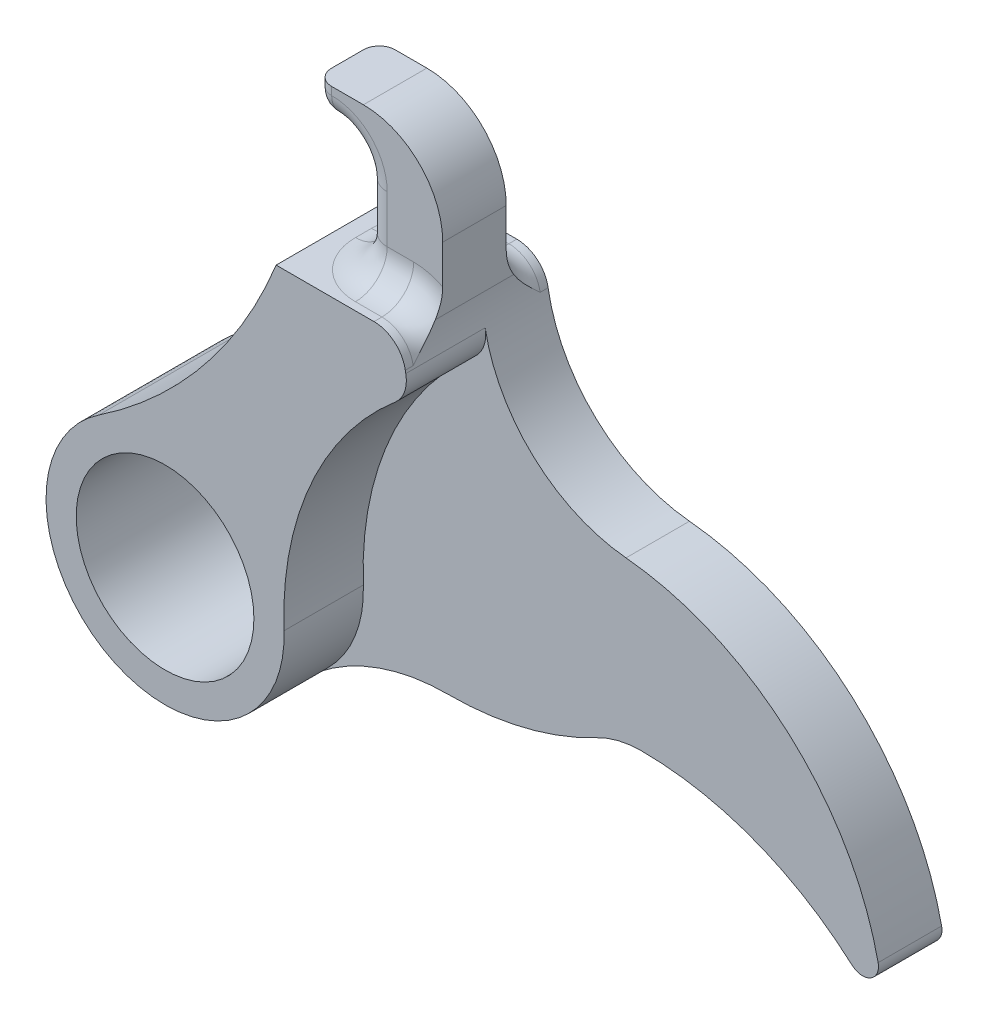
SolidWorks part; units mm, degrees
ref_plane "Спереди" through (0, 0, 0) normal (0, 0, 1) x (1, 0, 0)
ref_plane "Сверху" through (0, 0, 0) normal (0, 1, 0) x (1, 0, 0)
ref_plane "Справа" through (0, 0, 0) normal (1, 0, 0) x (0, 0, -1)
sketch "base" plane through (0, 0, 0) normal (0, 0, 1) x (1, 0, 0)
  line L0 (0, -25) -> (-25, -20) construction
  line L1 (0, 0) -> (9.5671, -23.097) construction
  line L2 (0, 0) -> (-9.5671, -23.097) construction
  line L3 (0, 0) -> (0, -25) construction
  line L4 (0, 0) -> (-2.4504, -24.8796) construction
  line L6 (0, 0) -> (-4.8773, -24.5196) construction
  line L7 (0, -25) -> (25, -20) construction
  line L11 (0, 0) -> (-7.2571, -23.9235) construction
  line L14 (0, 0) -> (7.2571, -23.9235) construction
  line L16 (0, 0) -> (4.8773, -24.5196) construction
  line L18 (0, 0) -> (2.4504, -24.8796) construction
  line L19 (-9.5671, -23.097) -> (9.5671, -23.097) construction
  arc A0 (-7.6537, -18.4776) -> (7.6537, -18.4776) centre (0, 0) ccw construction
  circle A1 centre (0, -25) radius 5 construction
  arc A6 (-9.5671, -23.097) -> (9.5671, -23.097) centre (0, 0) ccw construction
  point P12 (0, -20)
  dimension "D5" = 45
  dimension "D12" = 20
  dimension "ArmA" = 25
  dimension "ArmB" = 25.4951
  dimension "R" = 5
  dimension "base_offset" = 25
  dimension "stick_leverage" = 25
sketch "base-curve" plane through (0, 0, 0) normal (0, 0, 1) x (1, 0, 0)
  line L0 (0, -20) -> (0, -25) construction
  line L1 (0, 0) -> (-2.4504, -24.8796) construction
  line L2 (0, 0) -> (2.4504, -24.8796) construction
  line L5 (-25, -20) -> (0, -20) construction
  line L6 (0, -20) -> (25, -20) construction
  line L7 (10, -20) -> (10, 0) construction
  line L8 (-10, -20) -> (-10, 0) construction
  line L9 (-10, 0) -> (10, 0) construction
  line L10 (-25, -20) -> (-10, 0) construction
  line L11 (10, 0) -> (25, -20) construction
  line L13 (0, 0) -> (-4.8773, -24.5196) construction
  line L14 (0, 0) -> (4.8773, -24.5196) construction
  line L15 (0, 0) -> (-7.2571, -23.9235) construction
  line L16 (0, 0) -> (-9.5671, -23.097) construction
  line L17 (-2.2605, -20.5401) -> (-4.3096, -21.5787)
  line L18 (-4.3096, -21.5787) -> (-6.5058, -22.3844)
  line L19 (-6.5058, -22.3844) -> (-9.5586, -23.0612)
  line L20 (-9.5586, -23.0612) -> (-12.1501, -23.2901)
  line L21 (-2.5877, -26.2729) -> (-4.3096, -21.5787) construction
  line L22 (-8.4763, -27.9427) -> (-9.5586, -23.0612) construction
  line L23 (-5.4235, -27.2658) -> (-6.5058, -22.3844) construction
  line L24 (-11.7101, -28.2707) -> (-12.1501, -23.2901) construction
  line L25 (-22.6762, -27.1309) -> (-1.5492, -20.2461) construction
  line L26 (0, 0) -> (7.2571, -23.9235) construction
  line L27 (0, 0) -> (9.5671, -23.097) construction
  circle A0 centre (0, -25) radius 5 construction
  circle A1 centre (2.6465, -26.87) radius 5 construction
  circle A2 centre (-2.5877, -26.2729) radius 5 construction
  circle A4 centre (-5.4235, -27.2658) radius 5 construction
  circle A5 centre (-8.4763, -27.9427) radius 5 construction
  circle A6 centre (-25, -20) radius 7.5 construction
  circle A7 centre (-11.7101, -28.2707) radius 5 construction
  circle A8 centre (5.6576, -28.4428) radius 5 construction
  circle A9 centre (8.9988, -29.6652) radius 5 construction
  circle A10 centre (12.6286, -30.488) radius 5 construction
  point P3 (2.4504, -24.8796)
  point P11 (2.6465, -26.87)
  point P24 (-2.4504, -24.8796)
  point P25 (4.8773, -24.5196)
  point P27 (-4.8773, -24.5196)
  point P33 (-7.2571, -23.9235)
  point P36 (-9.5671, -23.097)
  point P39 (-2.5877, -26.2729)
  point P40 (5.6576, -28.4428)
  point P41 (-5.4235, -27.2658)
  point P42 (-8.4763, -27.9427)
  point P43 (-11.7101, -28.2707)
  point P64 (7.2571, -23.9235)
  point P65 (8.9988, -29.6652)
  point P68 (9.5671, -23.097)
  point P69 (12.6286, -30.488)
  dimension "D13" = 15
  dimension "spring" = 20
  dimension "b_long" = 53.13
  dimension "b_short" = 53.13
  dimension "D3" = 1.4
  dimension "D4" = 2.8
  dimension "D5" = 4.2
  dimension "D6" = 5.6
  dimension "D2" = 2
  dimension "D7" = 4
  dimension "D8" = 6
  dimension "D9" = 8
sketch "Эскиз2" plane through (0, 0, 0) normal (0, 0, 1) x (1, 0, 0)
  line L0 (-11.7101, -28.2707) -> (-12.1749, -23.0095) construction
  line L1 (-10, 0) -> (-18, 0) construction
  line L3 (-2.2605, -20.5401) -> (-4.3096, -21.5787) construction
  line L4 (0, -25) -> (0, 0) construction
  line L10 (-4.3096, -21.5787) -> (-6.5058, -22.3844) construction
  line L11 (-22.6602, -27.1257) -> (-1.8719, -20.2995) construction
  line L12 (-6.5058, -22.3844) -> (-9.5586, -23.0612) construction
  line L13 (-9.5586, -23.0612) -> (-12.1501, -23.2901) construction
  line L14 (-2.2605, -20.5401) -> (-4.3096, -21.5787) construction
  line L15 (-4.3096, -21.5787) -> (-6.5058, -22.3844) construction
  line L16 (-6.5058, -22.3844) -> (-9.5586, -23.0612) construction
  line L17 (-9.5586, -23.0612) -> (-12.1501, -23.2901) construction
  line L19 (0, -25) -> (0, -40) construction
  line L20 (0, -40) -> (15.3209, -27.1442) construction
  line L21 (-18, 0) -> (-15, 0)
  line L23 (-10, 0) -> (-10, 7)
  line L24 (-10, 7) -> (-15, 7)
  line L25 (-15, 0) -> (-15, 7)
  circle A0 centre (-25, -20) radius 7.5 construction
  arc A1 (-2.8021, -20.6945) -> (-12.1749, -23.0095) centre (-12.1425, -3.0096) cw
  arc A2 (-29.1682, -13.7649) -> (-20.3156, -25.8571) centre (-25, -20) ccw
  arc A3 (15.3209, -27.1442) -> (0, -20) centre (0, -40) ccw
  arc A5 (-29.1682, -13.7649) -> (-18, 0) centre (-45.8408, 11.1755) ccw
  arc A6 (-7.6537, -18.4776) -> (7.6537, -18.4776) centre (0, 0) ccw construction
  arc A7 (-9.5671, -23.097) -> (9.5671, -23.097) centre (0, 0) ccw construction
  arc A8 (-2.8021, -20.6945) -> (0, -20) centre (0, -26) cw
  arc A10 (15.3209, -27.1442) -> (-0.9516, -9.9546) centre (-2.6644, -27.8729) ccw
  arc A11 (-0.9516, -9.9546) -> (-10, 0) centre (0, 0) cw
  arc A13 (-16.899, -23.8901) -> (-9.55, -2.9661) centre (2.4797, -18.9437) cw construction
  arc A17 (-20.3156, -25.8571) -> (-12.1749, -23.0095) centre (-12.1959, -36.0095) cw
  point P48 (-2.5877, -26.2729)
  point P52 (-5.4235, -27.2658)
  point P54 (-8.4763, -27.9427)
  point P56 (-11.7101, -28.2707)
  dimension "D2" = 6
  dimension "D3" = 5
  dimension "D4" = 3
  dimension "D5" = 30
  dimension "D6" = 50
  dimension "D8" = 18
  dimension "80" = 20
  dimension "D9" = 20
  dimension "D10" = 20
  dimension "D11" = 7
  dimension "D14" = 13
  dimension "D7" = 10
  dimension "D1" = 8
extrude "Бобышка-Вытянуть1" add sketch "Эскиз2" along normal blind 9
sketch "Эскиз6" plane through (0, 0, 9) normal (0, 0, 1) x (1, 0, 0)
  arc A0 (-9.55, -2.9661) -> (-16.899, -23.8901) centre (2.4797, -18.9437) ccw construction
  arc A1 (-9.55, -2.9661) -> (-16.899, -23.8901) centre (2.4797, -18.9437) ccw
  arc A2 (15.3209, -27.1442) -> (-0.9516, -9.9546) centre (-2.6644, -27.8729) ccw construction
  arc A3 (-12.1749, -23.0095) -> (-20.3156, -25.8571) centre (-12.1959, -36.0095) ccw construction
  arc A4 (15.3209, -27.1442) -> (0, -20) centre (0, -40) ccw construction
  arc A5 (-10, 0) -> (-0.9516, -9.9546) centre (0, 0) ccw construction
  arc A6 (15.3209, -27.1442) -> (-0.9516, -9.9546) centre (-2.6644, -27.8729) ccw
  arc A7 (-9.55, -2.9661) -> (-0.9516, -9.9546) centre (0, 0) ccw
  arc A8 (15.3209, -27.1442) -> (0, -20) centre (0, -40) ccw
  arc A9 (-12.1749, -23.0095) -> (-2.8021, -20.6945) centre (-12.1425, -3.0096) ccw construction
  arc A10 (0, -20) -> (-2.8021, -20.6945) centre (0, -26) ccw construction
  arc A11 (-12.1749, -23.0095) -> (-16.899, -23.8901) centre (-12.1959, -36.0095) ccw
  arc A12 (-12.1749, -23.0095) -> (-2.8021, -20.6945) centre (-12.1425, -3.0096) ccw
  arc A13 (0, -20) -> (-2.8021, -20.6945) centre (0, -26) ccw
extrude "Вырез-Вытянуть1" cut sketch "Эскиз6" against normal blind 5
sketch "Эскиз12" plane through (-15, 0, 0) normal (-1, 0, 0) x (0, 0, 1)
  line L0 (9, 0) -> (0, 0) construction
  line L1 (0, 7) -> (2.5, 7)
  line L2 (0, 7) -> (0, 0)
  line L3 (0, 0) -> (2.5, 0)
  line L4 (2.5, 7) -> (2.5, 0)
  line L5 (4.5, 0) -> (4.5, 7) construction
  line L6 (9, 7) -> (0, 7) construction
  line L7 (6.5, 7) -> (6.5, 0)
  line L8 (9, 0) -> (6.5, 0)
  line L9 (9, 7) -> (9, 0)
  line L10 (9, 7) -> (6.5, 7)
  dimension "D1" = 4
extrude "Вырез-Вытянуть3" cut sketch "Эскиз12" against normal through all
fillet "Скругление11" radius 2 2 edges at (-10, 0, 1.25) (-10, 0, 7.75)
fillet "Скругление1" radius 1 1 edges at (15.3209, -27.1442, 2)
sketch "Эскиз10" plane through (0, 7, 0) normal (0, 1, 0) x (-1, 0, 0)
  line L0 (10, 6.5) -> (15, 6.5) construction
  line L1 (10, 2.5) -> (18, 2.5)
  line L2 (10, 2.5) -> (10, 6.5)
  line L3 (10, 6.5) -> (18, 6.5)
  line L4 (18, 2.5) -> (18, 6.5)
  line L5 (10, 6.5) -> (10, 2.5) construction
  line L6 (15, 6.5) -> (15, 2.5) construction
  dimension "D1" = 3
extrude "Бобышка-Вытянуть3" add sketch "Эскиз10" along normal blind 2
fillet "Скругление5" radius 5 1 edges at (-10, 9, 4.5)
fillet "Скругление10" radius 7.5 1 edges at (-16.899, -23.8901, 6.5)
fillet "Скругление14" radius 2 1 edges
fillet "Скругление15" radius 1.5 6 edges at (-15.5858, 6.4142, 2.5) (-15.5858, 6.4142, 6.5)
fillet "Скругление16" radius 2 7 edges at (-10.5412, -0.4725, 6.5) (-12.6661, 0, 6.5) (-10.5412, -0.4725, 2.5) (-12.6661, 0, 2.5) (-14.5607, 0, 2.9393) (-15, 0, 4.5) (-14.5607, 0, 6.0607)
fillet "Скругление17" radius 1 5 edges at (-18, 8.75, 2.5) (-18, 7.4393, 2.9393) (-18, 7, 4.5) (-18, 8.75, 6.5) (-18, 7.4393, 6.0607)
fillet "Скругление18" radius 2 1 edges at (-9.55, -2.9661, 6.5)
sketch "Эскиз11" plane through (0, 0, 9) normal (0, 0, 1) x (1, 0, 0)
  circle A0 centre (-25, -20) radius 5.5 construction
  arc A1 (-29.1682, -13.7649) -> (-20.3156, -25.8571) centre (-25, -20) ccw construction
  circle A2 centre (-25, -20) radius 5.6
  dimension "D1" = 11
  dimension "tolerance" = 0.1
extrude "Вырез-Вытянуть2" cut sketch "Эскиз11" against normal through all
equation "\"rad\"= 0.0174533"
equation "\"radius_offset\"= 10"
equation "\"spring_power\"= 200'g"
equation "\"D4@base-curve\"=\"D3@base-curve\"*2"
equation "\"D5@base-curve\"=\"D3@base-curve\"*3"
equation "\"D6@base-curve\"=\"D3@base-curve\"*4"
equation "\"D7@base-curve\"=\"D2@base-curve\"*2"
equation "\"D8@base-curve\"=\"D2@base-curve\"*3"
equation "\"D9@base-curve\"=\"D2@base-curve\"*4"
